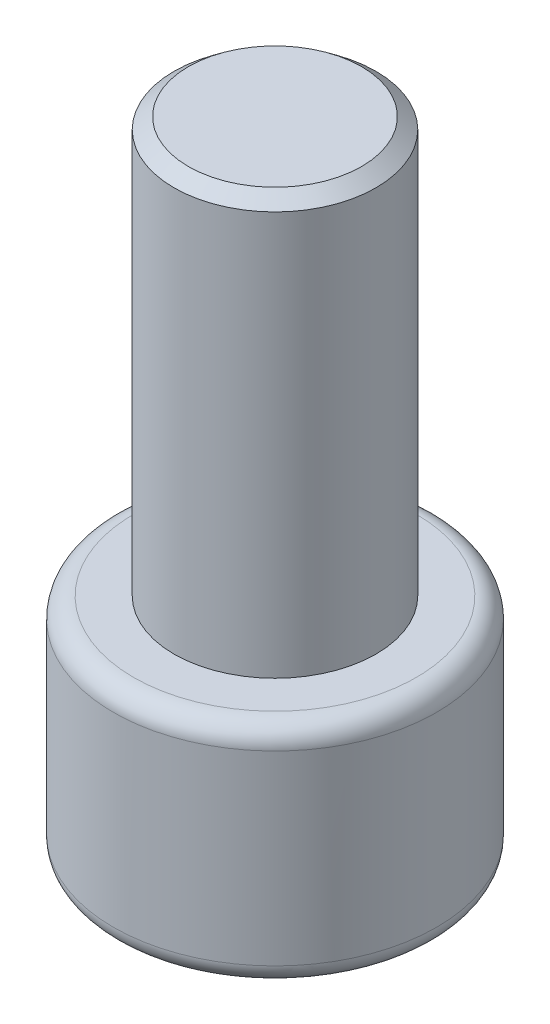
SolidWorks part; units mm, degrees
material "AISI 1020"
ref_plane "Alzado" through (0, 0, 0) normal (0, 0, 1) x (1, 0, 0)
ref_plane "Planta" through (0, 0, 0) normal (0, 1, 0) x (1, 0, 0)
ref_plane "Vista lateral" through (0, 0, 0) normal (1, 0, 0) x (0, 0, -1)
sketch "Croquis1" plane through (0, 0, 0) normal (0, 0, 1) x (1, 0, 0)
  line L0 (0, 0) -> (0, 85.9498) construction
  line L1 (-5, 31.2164) -> (-5, 11.2164)
  line L2 (-5, 11.2164) -> (-15.9235, 2.682) construction
  line L3 (-15, 0) -> (0, 0) construction
  line L4 (-15, 0) -> (-15, 5.5806) construction
  line L5 (-15.9235, 2.682) -> (-8, -7.4596) construction
  line L6 (-5, 31.2164) -> (-4.2883, 31.7724)
  line L7 (-4.2883, 31.7724) -> (0, 31.7724)
  line L8 (-5, 31.2164) -> (1.4006, 31.2164) construction
  line L9 (0, 0) -> (0, 31.7724)
  line L10 (-5, 11.2164) -> (-8, 11.2164)
  line L11 (-8, 11.2164) -> (-8, 0)
  line L12 (-8, 0) -> (0, 0)
  arc A0 (-15.9235, 2.682) -> (-15, 0) centre (-15, 1.5) ccw construction
  point P10 (-15, 1.5)
  dimension "D2" = 1.5
  dimension "D5" = 8
  dimension "D1" = 38
  dimension "D3" = 15
  dimension "D4" = 5
  dimension "D6" = 20
  dimension "D7" = 38
  dimension "D8" = 4.2883
revolve "Revolución2" add sketch "Croquis1" angle 360 about L0 region at (-3.1976, 14.0717, 0)
sketch "Croquis2" plane through (0, 0, 0) normal (0, -1, 0) x (1, 0, 0)
  line L1 (0, 5.1962) -> (-4.5, 2.5981)
  line L2 (-4.5, 2.5981) -> (-4.5, -2.5981)
  line L3 (-4.5, -2.5981) -> (0, -5.1962)
  line L4 (0, -5.1962) -> (4.5, -2.5981)
  line L5 (4.5, -2.5981) -> (4.5, 2.5981)
  line L6 (4.5, 2.5981) -> (0, 5.1962)
  circle A0 centre (0, 0) radius 4.5 construction
  point P1 (0, 0)
  dimension "D1" = 9
extrude "Cortar-Extruir1" cut sketch "Croquis2" against normal blind 7
fillet "Redondeo1" radius 1 2 edges at (0, 0, -8) (0, 11.2164, -8)
